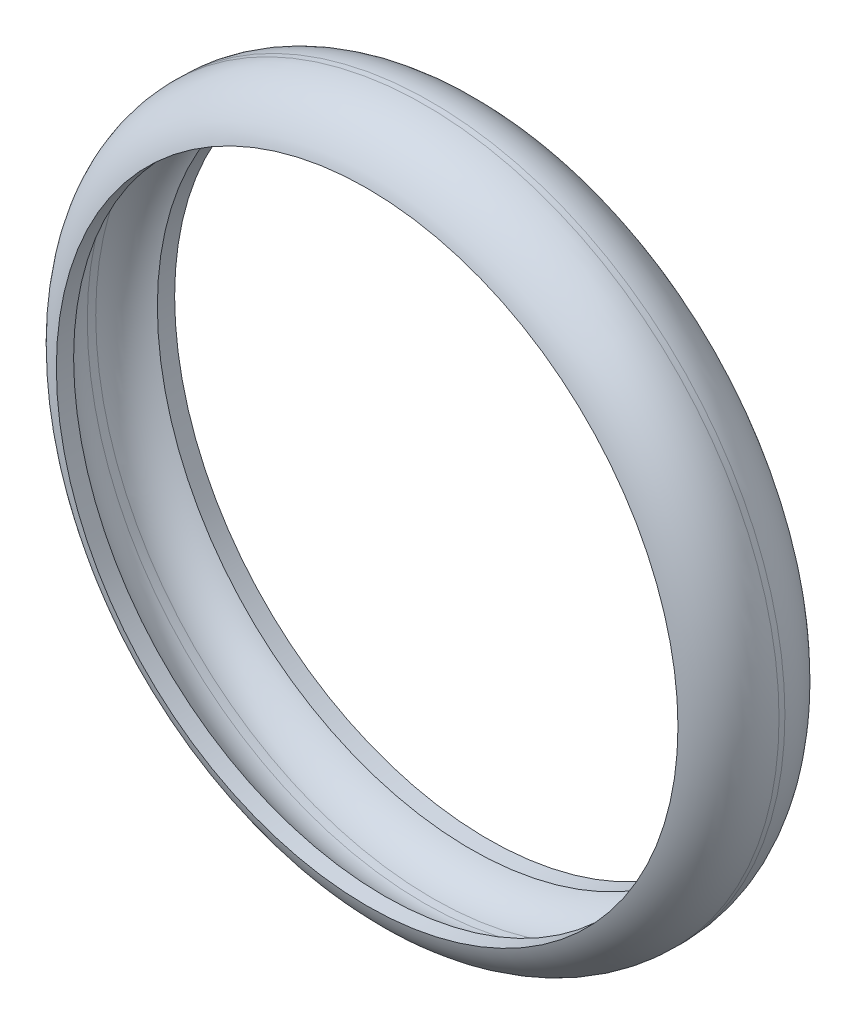
SolidWorks part; units mm, degrees
material "ABS"
ref_plane "Alzado" through (0, 0, 0) normal (0, 0, 1) x (1, 0, 0)
ref_plane "Planta" through (0, 0, 0) normal (0, 1, 0) x (1, 0, 0)
ref_plane "Vista lateral" through (0, 0, 0) normal (1, 0, 0) x (0, 0, -1)
sketch "Sketch1" plane through (0, 0, 0) normal (0, 0, 1) x (1, 0, 0)
  circle A0 centre (0, 0) radius 39
  circle A1 centre (0, 0) radius 41
  dimension "D1" = 78
  dimension "D2" = 2
extrude "Boss-Extrude1" add sketch "Sketch1" along normal blind 10
sketch "Sketch2" plane through (0, 0, 10) normal (0, 0, 1) x (1, 0, 0)
  circle A0 centre (0, 0) radius 41
  circle A1 centre (0, 0) radius 36
  circle A2 centre (0, 0) radius 41 construction
  dimension "D1" = 5
extrude "Boss-Extrude2" add sketch "Sketch2" along normal blind 2
sketch "Sketch3" plane through (0, 0, 0) normal (0, 0, -1) x (-1, 0, 0)
  circle A0 centre (0, 0) radius 41
  circle A1 centre (0, 0) radius 36.3
  circle A2 centre (0, 0) radius 41 construction
extrude "Boss-Extrude3" add sketch "Sketch3" along normal blind 2
fillet "Fillet2" radius 5 2 edges at (39, 0, 10) (39, 0, 0)
fillet "Fillet6" radius 7 2 edges at (-41, 0, -2) (41, 0, 12)
